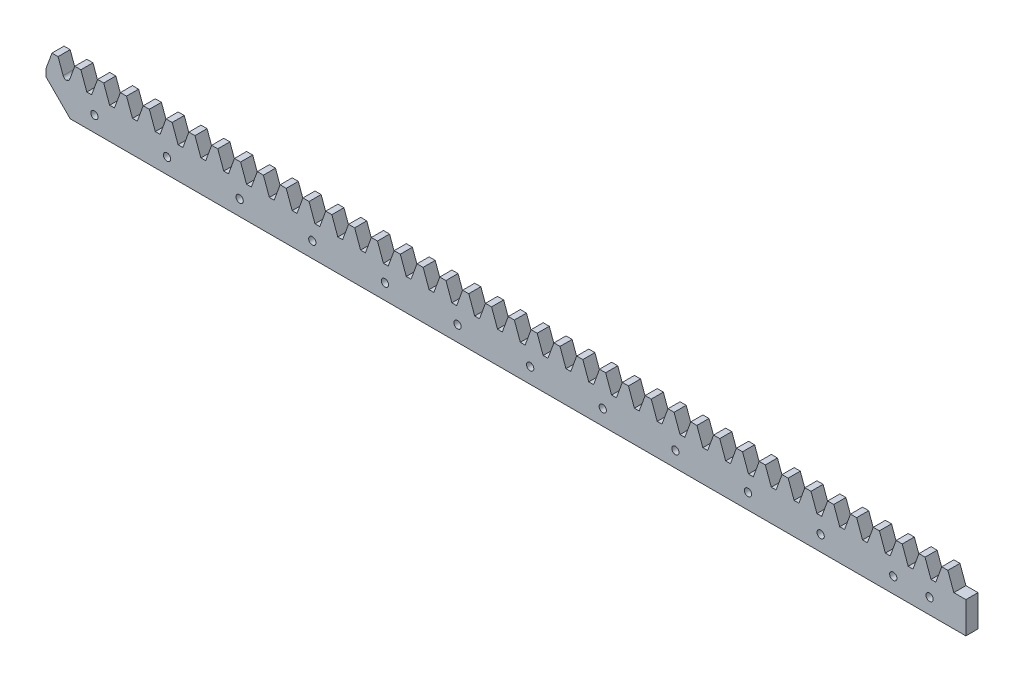
SolidWorks part; units mm, degrees
material "Thornel Mat VMA"
ref_plane "前视基准面" through (0, 0, 0) normal (0, 0, 1) x (1, 0, 0)
ref_plane "上视基准面" through (0, 0, 0) normal (0, 1, 0) x (1, 0, 0)
ref_plane "右视基准面" through (0, 0, 0) normal (1, 0, 0) x (0, 0, -1)
sketch "草图1" plane through (0, 0, 0) normal (0, 0, 1) x (1, 0, 0)
  line L1 (0, 0) -> (380, 0)
  line L2 (0, 0) -> (0, -10)
  line L3 (0, -10) -> (380, -10)
  line L4 (380, 0) -> (380, -10)
  dimension "D1" = 10
  dimension "L" = 380
extrude "拉伸1" add sketch "草图1" along normal blind 5
sketch "草图2" plane through (0, 0, 5) normal (0, 0, 1) x (1, 0, 0)
  line L0 (0, 0) -> (2.4568, 6.75)
  line L1 (2.4568, 6.75) -> (4.9854, 6.75)
  line L2 (4.9854, 6.75) -> (7.4422, 0)
  line L3 (380, 0) -> (0, 0) construction
  line L4 (0, 0) -> (7.4422, 0)
  line L5 (1.3649, 3.75) -> (6.0773, 3.75) construction
  dimension "D2" = 70
  dimension "alpha" = 110
  dimension "ha" = 3
  dimension "hf" = 3.75
  dimension "S" = 4.7124
extrude "拉伸2" add sketch "草图2" against normal up to surface (5 mm away) up to face at (190, -5, 0)
sketch "草图3" plane through (0, 0, 5) normal (0, 0, 1) x (1, 0, 0)
  line L2 (3.7211, 6.75) -> (3.7211, -10) construction
  line L3 (4.9854, 6.75) -> (2.4568, 6.75) construction
  line L4 (380, 1.5) -> (8.4925, 1.5)
  line L5 (8.4925, 1.5) -> (6.3949, 7.263)
  line L6 (380, 1.5) -> (8.4925, 1.5) construction
  line L7 (8.4925, 1.5) -> (6.3949, 7.263) construction
  line L8 (0, -10) -> (380, -10) construction
  circle A0 centre (8.4925, 1.5) radius 2
  circle A1 centre (-1.0503, 1.5) radius 2
  dimension "D2" = 4
  dimension "D1" = 1.5
extrude "切除-拉伸1" [suppressed] cut sketch "草图3" against normal through all
pattern_linear "阵列(线性)1" count 40 spacing 9.4248 along (1, 0, 0) of "拉伸2"
fillet "圆角1" radius 1.5 2 edges at (9.4248, 0, 2.5)
sketch "草图4" plane through (0, -10, 0) normal (0, -1, 0) x (1, 0, 0)
  line L1 (0, 5) -> (380, 5)
  line L2 (0, 5) -> (0, 0)
  line L3 (0, 0) -> (380, 0)
  line L4 (380, 5) -> (380, 0)
extrude "凸台-拉伸1" add sketch "草图4" along normal blind 3
chamfer "倒角1" distance 10 angle 45 1 edges at (0, -13, 2.5)
sketch "草图5" plane through (0, 0, 5) normal (0, 0, 1) x (1, 0, 0)
  line L0 (380, -13) -> (10, -13) construction
  line L1 (380, -13) -> (380, 0) construction
  circle A0 centre (365, -6.65) radius 1.5
  circle A1 centre (350, -6.65) radius 1.5
  circle A2 centre (320, -6.65) radius 1.5
  circle A3 centre (290, -6.65) radius 1.5
  circle A4 centre (260, -6.65) radius 1.5
  circle A5 centre (230, -6.65) radius 1.5
  circle A6 centre (200, -6.65) radius 1.5
  circle A7 centre (170, -6.65) radius 1.5
  circle A8 centre (140, -6.65) radius 1.5
  circle A9 centre (110, -6.65) radius 1.5
  circle A10 centre (80, -6.65) radius 1.5
  circle A11 centre (50, -6.65) radius 1.5
  circle A12 centre (20, -6.65) radius 1.5
  dimension "D1" = 6.35
  dimension "D2" = 15
  dimension "D3" = 3
  dimension "D4" = 2
  dimension "D5" = 12
extrude "切除-拉伸2" cut sketch "草图5" against normal through all
equation "\"D2@草图2\" = 180 - \"alpha@草图2\""
equation "\"Z@阵列(线性)1\"=40"
equation "\"D3@阵列(线性)1\"=\"S@草图2\" * 2mm"
